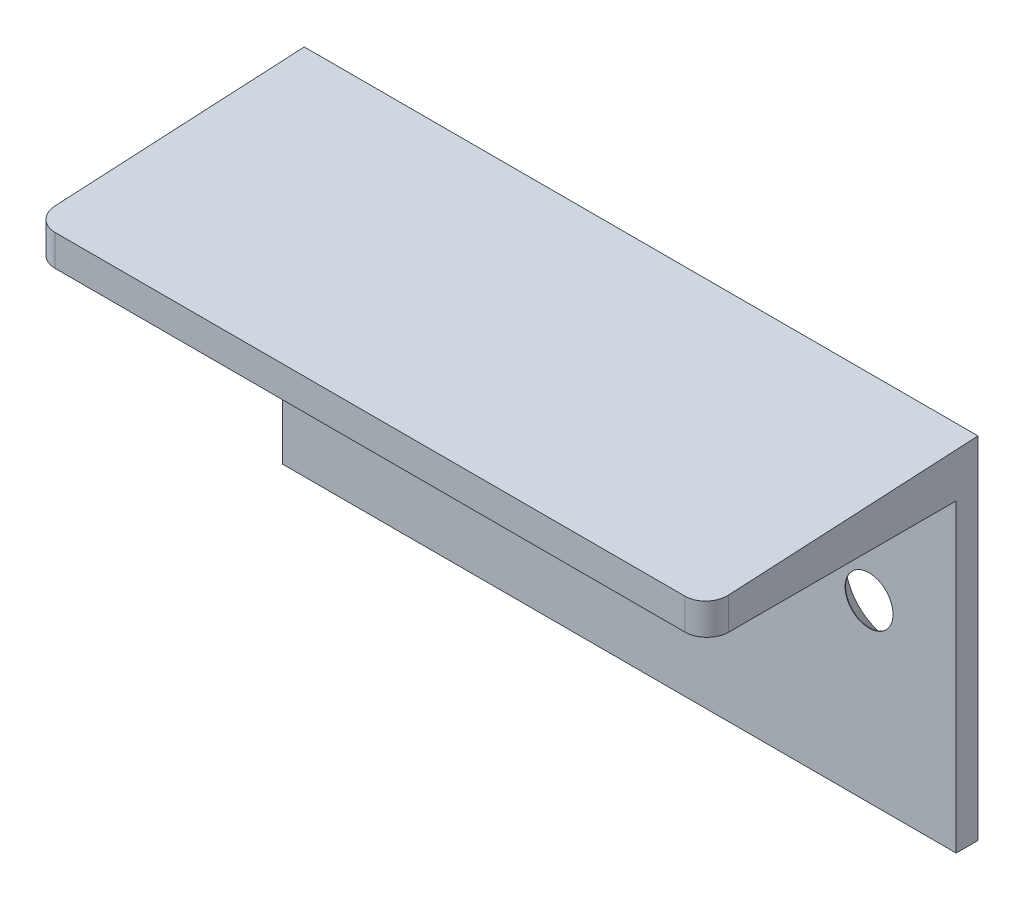
SolidWorks part; units mm, degrees
material "6061 Alloy"
ref_plane "Top Plane" through (0, 0, 0) normal (0, 0, 1) x (1, 0, 0)
ref_plane "Front Plane" through (0, 0, 0) normal (0, 1, 0) x (1, 0, 0)
ref_plane "Right Plane" through (0, 0, 0) normal (1, 0, 0) x (0, 0, -1)
sketch "Sketch1" plane through (0, 0, 0) normal (0, 0, 1) x (1, 0, 0)
  line L1 (-38.65, -20.1) -> (38.65, -20.1)
  line L2 (-38.65, -20.1) -> (-38.65, 20.1)
  line L3 (-38.65, 20.1) -> (38.65, 20.1)
  line L4 (38.65, -20.1) -> (38.65, 20.1)
  line L5 (-38.65, -20.1) -> (38.65, 20.1) construction
  line L6 (-38.65, 20.1) -> (38.65, -20.1) construction
  point P0 (0, 0)
  dimension "D1" = 40.2
  dimension "D2" = 77.3
extrude "Boss-Extrude1" add sketch "Sketch1" along normal blind 2.5
sketch "Sketch3" plane through (0, 0, 2.5) normal (0, 0, 1) x (1, 0, 0)
  line L0 (38.65, -20.1) -> (38.65, 20.1) construction
  line L1 (-38.65, 20.1) -> (38.65, 20.1)
  line L2 (-38.65, 20.1) -> (-38.65, 14.9)
  line L3 (-38.65, 14.9) -> (38.65, 14.9)
  line L4 (38.65, 20.1) -> (38.65, 14.9)
  dimension "D1" = 5.2
extrude "Boss-Extrude2" add sketch "Sketch3" along normal blind 28.599
fillet "Fillet1" radius 2.5 2 edges at (-38.65, 17.5, 31.099) (38.65, 17.5, 31.099)
sketch "Sketch4" plane through (0, 20.1, 0) normal (0, 1, 0) x (1, 0, 0)
  line L0 (38.65, 0) -> (-38.65, 0) construction
  line L1 (-38.65, 0) -> (38.65, 0)
  line L2 (-38.65, 0) -> (-38.65, -37.3428)
  line L3 (-38.65, -37.3428) -> (38.65, -37.3428)
  line L4 (38.65, 0) -> (38.65, -37.3428)
  line L5 (-38.65, -28.599) -> (-38.65, 0) construction
  point P8 (51.45, 0)
revolve "Cut-Revolve2" cut sketch "Sketch4" angle 3 about L1
hole_wizard "CSK for M5 Flat Head Machine Screw1" positions "Sketch5" profile "Sketch6" countersink size "M5" standard "ANSI Metric"
sketch "Sketch5" plane through (0, 0, 0) normal (0, 0, -1) x (-1, 0, 0)
  line L0 (-38.65, -20.1) -> (-38.65, 20.1) construction
  line L1 (38.65, 20.1) -> (38.65, -20.1) construction
  line L2 (-38.65, 20.1) -> (38.65, 20.1) construction
  point P0 (-28.65, 0)
  point P2 (28.65, 0)
  dimension "D1" = 10
  dimension "D2" = 10
  dimension "D3" = 20.1
  dimension "D4" = 20.1
sketch "Sketch6" plane through (28.65, 0, 0) normal (1, 0, 0) x (0, 1, 0)
  line L0 (0, 0) -> (0, 14.0524)
  line L1 (0, 14.0524) -> (2.75, 12.4)
  line L2 (2.75, 12.4) -> (2.75, 2.45)
  line L3 (2.75, 2.45) -> (5.2, 0)
  line L5 (5.2, 0) -> (0, 0)
  line L6 (-2.75, 2.45) -> (-5.2, 0) construction
  line L10 (0, 14.0524) -> (-2.75, 12.4) construction
  line L11 (0, -6.35) -> (0, 107.95) construction
  dimension "Hole Dia." = 5.5
  dimension "Hole Depth" = 12.4
  dimension "Near C'Sink Dia." = 10.4
  dimension "Near C'Sink Angle" = 90
  dimension "Drill Angle" = 118
